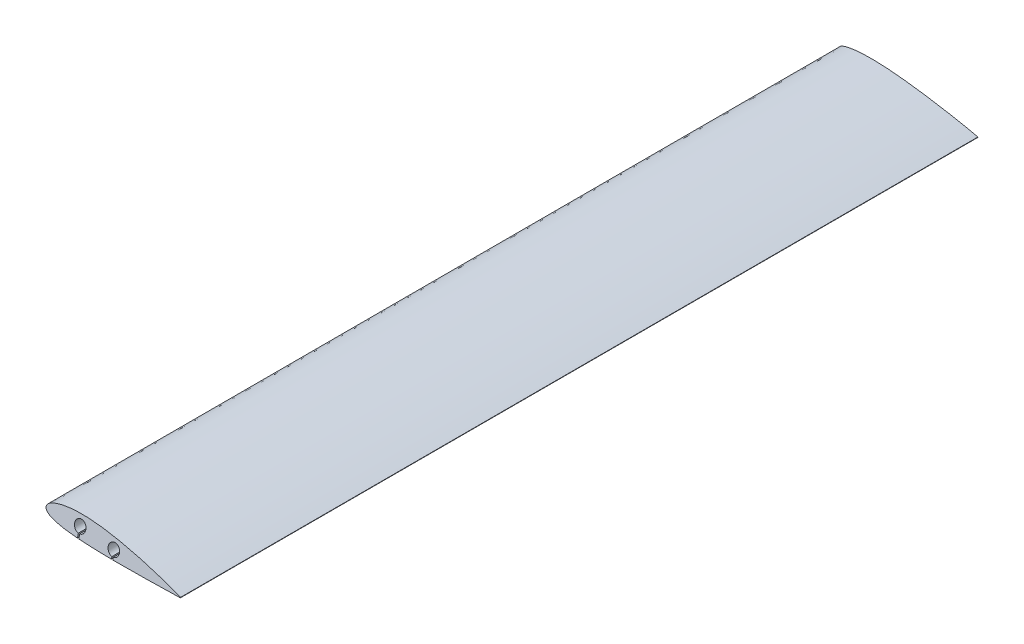
SolidWorks part; units mm, degrees
material "Custom Plastic"
ref_plane "Front Plane" through (0, 0, 0) normal (0, 0, 1) x (1, 0, 0)
ref_plane "Top Plane" through (0, 0, 0) normal (0, 1, 0) x (1, 0, 0)
ref_plane "Right Plane" through (0, 0, 0) normal (1, 0, 0) x (0, 0, -1)
curve "Curve1"
  spline degree 3 poles (119.72, -8.1948, 0) (119.6176, -8.1622, 0) (119.1985, -8.0289, 0) (118.2498, -7.745, 0) (116.6764, -7.2682, 0) (114.4937, -6.6229, 0) (111.726, -5.8198, 0) (108.3989, -4.8842, 0) (104.5474, -3.8358, 0) (100.2105, -2.7001, 0) (95.4335, -1.5003, 0) (90.2667, -0.2644, 0) (84.7642, 0.9828, 0) (78.9848, 2.2132, 0) (72.9906, 3.4008, 0) (66.8472, 4.5234, 0) (60.6201, 5.5483, 0) (54.3772, 6.4571, 0) (48.1692, 7.2302, 0) (42.0621, 7.8148, 0) (36.1259, 8.1773, 0) (30.4496, 8.3149, 0) (25.1001, 8.227, 0) (20.1405, 7.9255, 0) (15.6293, 7.4181, 0) (11.6181, 6.7322, 0) (8.1521, 5.8882, 0) (5.2655, 4.9177, 0) (2.98, 3.8441, 0) (1.3063, 2.6841, 0) (0.2335, 1.4154, 0) (-0.1257, -0.004, 0) (0.316, -1.3971, 0) (1.4469, -2.6023, 0) (3.1553, -3.6733, 0) (5.4426, -4.65, 0) (8.2964, -5.5286, 0) (11.6917, -6.304, 0) (15.5927, -6.9754, 0) (19.9599, -7.5398, 0) (24.7472, -8.002, 0) (29.9056, -8.3725, 0) (35.3823, -8.6597, 0) (41.1213, -8.8812, 0) (47.0817, -9.0555, 0) (53.2028, -9.1881, 0) (59.4204, -9.2536, 0) (65.6487, -9.2717, 0) (71.8184, -9.2592, 0) (77.8616, -9.2203, 0) (83.7119, -9.1645, 0) (89.3044, -9.1004, 0) (94.5769, -9.0293, 0) (99.4704, -8.9537, 0) (103.9296, -8.8805, 0) (107.904, -8.8075, 0) (111.3483, -8.7373, 0) (114.2228, -8.6769, 0) (116.4943, -8.6239, 0) (118.1358, -8.5859, 0) (119.1326, -8.5579, 0) (119.5801, -8.549, 0) (119.6954, -8.5467, 0) knots 0 0 0 0 0.001308 0.005358 0.012063 0.021337 0.033087 0.047171 0.063441 0.081714 0.101785 0.123442 0.146433 0.170517 0.195424 0.220875 0.246594 0.272302 0.297725 0.322799 0.347029 0.370162 0.391954 0.412188 0.43067 0.447231 0.461732 0.474085 0.484276 0.492392 0.498749 0.5041 0.509453 0.51579 0.523838 0.533885 0.546005 0.560171 0.576284 0.594211 0.613803 0.634869 0.65721 0.680611 0.704835 0.729853 0.755197 0.780583 0.805729 0.830359 0.854204 0.877002 0.898494 0.918443 0.936623 0.952826 0.966868 0.978592 0.987852 0.994547 0.998596 1 1 1 1
sketch "Sketch4" plane through (0, 0, 0) normal (0, 0, 1) x (1, 0, 0)
  line L0 (119.72, -8.1948) -> (119.6954, -8.5467)
  line L1 (0, 0) -> (162.2931, 0) construction
  spline S2 degree 3 poles (1370.0357, 3790.6471) (156.0859, -40.1115) (140.424, -14.3791) (118.2498, -7.745) (116.6764, -7.2682) (114.4937, -6.6229) (111.726, -5.8198) (108.3989, -4.8842) (104.5474, -3.8358) (100.2105, -2.7001) (95.4335, -1.5003) (90.2667, -0.2644) (84.7642, 0.9828) (78.9848, 2.2132) (72.9906, 3.4008) (66.8472, 4.5234) (60.6201, 5.5483) (54.3772, 6.4571) (48.1692, 7.2302) (42.0621, 7.8148) (36.1259, 8.1773) (30.4496, 8.3149) (25.1001, 8.227) (20.1405, 7.9255) (15.6293, 7.4181) (11.6181, 6.7322) (8.1521, 5.8882) (5.2655, 4.9177) (2.98, 3.8441) (1.3063, 2.6841) (0.2335, 1.4154) (-0.1257, -0.004) (0.316, -1.3971) (1.4469, -2.6023) (3.1553, -3.6733) (5.4426, -4.65) (8.2964, -5.5286) (11.6917, -6.304) (15.5927, -6.9754) (19.9599, -7.5398) (24.7472, -8.002) (29.9056, -8.3725) (35.3823, -8.6597) (41.1213, -8.8812) (47.0817, -9.0555) (53.2028, -9.1881) (59.4204, -9.2536) (65.6487, -9.2717) (71.8184, -9.2592) (77.8616, -9.2203) (83.7119, -9.1645) (89.3044, -9.1004) (94.5769, -9.0293) (99.4704, -8.9537) (103.9296, -8.8805) (107.904, -8.8075) (111.3483, -8.7373) (114.2228, -8.6769) (116.4943, -8.6239) (118.1358, -8.5859) (148.3455, -7.7372) (178.3806, -23.1567) (115.1651, 3990.3657) knots -0.26989 -0.26989 -0.26989 -0.26989 0.001308 0.005358 0.012063 0.021337 0.033087 0.047171 0.063441 0.081714 0.101785 0.123442 0.146433 0.170517 0.195424 0.220875 0.246594 0.272302 0.297725 0.322799 0.347029 0.370162 0.391954 0.412188 0.43067 0.447231 0.461732 0.474085 0.484276 0.492392 0.498749 0.5041 0.509453 0.51579 0.523838 0.533885 0.546005 0.560171 0.576284 0.594211 0.613803 0.634869 0.65721 0.680611 0.704835 0.729853 0.755197 0.780583 0.805729 0.830359 0.854204 0.877002 0.898494 0.918443 0.936623 0.952826 0.966868 0.978592 0.987852 0.994547 0.998596 1.35602 1.35602 1.35602 1.35602 only from (119.72, -8.1948) to (119.6954, -8.5467)
  spline S3 degree 3 poles (119.72, -8.1948) (119.6176, -8.1622) (119.1985, -8.0289) (118.2498, -7.745) (116.6764, -7.2682) (114.4937, -6.6229) (111.726, -5.8198) (108.3989, -4.8842) (104.5474, -3.8358) (100.2105, -2.7001) (95.4335, -1.5003) (90.2667, -0.2644) (84.7642, 0.9828) (78.9848, 2.2132) (72.9906, 3.4008) (66.8472, 4.5234) (60.6201, 5.5483) (54.3772, 6.4571) (48.1692, 7.2302) (42.0621, 7.8148) (36.1259, 8.1773) (30.4496, 8.3149) (25.1001, 8.227) (20.1405, 7.9255) (15.6293, 7.4181) (11.6181, 6.7322) (8.1521, 5.8882) (5.2655, 4.9177) (2.98, 3.8441) (1.3063, 2.6841) (0.2335, 1.4154) (-0.1257, -0.004) (0.316, -1.3971) (1.4469, -2.6023) (3.1553, -3.6733) (5.4426, -4.65) (8.2964, -5.5286) (11.6917, -6.304) (15.5927, -6.9754) (19.9599, -7.5398) (24.7472, -8.002) (29.9056, -8.3725) (35.3823, -8.6597) (41.1213, -8.8812) (47.0817, -9.0555) (53.2028, -9.1881) (59.4204, -9.2536) (65.6487, -9.2717) (71.8184, -9.2592) (77.8616, -9.2203) (83.7119, -9.1645) (89.3044, -9.1004) (94.5769, -9.0293) (99.4704, -8.9537) (103.9296, -8.8805) (107.904, -8.8075) (111.3483, -8.7373) (114.2228, -8.6769) (116.4943, -8.6239) (118.1358, -8.5859) (119.1326, -8.5579) (119.5801, -8.549) (119.6954, -8.5467) knots 0 0 0 0 0.001308 0.005358 0.012063 0.021337 0.033087 0.047171 0.063441 0.081714 0.101785 0.123442 0.146433 0.170517 0.195424 0.220875 0.246594 0.272302 0.297725 0.322799 0.347029 0.370162 0.391954 0.412188 0.43067 0.447231 0.461732 0.474085 0.484276 0.492392 0.498749 0.5041 0.509453 0.51579 0.523838 0.533885 0.546005 0.560171 0.576284 0.594211 0.613803 0.634869 0.65721 0.680611 0.704835 0.729853 0.755197 0.780583 0.805729 0.830359 0.854204 0.877002 0.898494 0.918443 0.936623 0.952826 0.966868 0.978592 0.987852 0.994547 0.998596 1 1 1 1
  dimension "D1" = 0
extrude "Boss-Extrude2" add sketch "Sketch4" along normal mid plane 700
sketch "Sketch5" plane through (0, 0, -350) normal (0, 0, -1) x (-1, 0, 0)
  line L1 (-30, 0) -> (-29.4, 0) construction
  line L2 (-29.4, 0) -> (-29.4, -8.3234)
  line L3 (-30, 0) -> (-30.6, 0) construction
  line L4 (-30.6, 0) -> (-30.6, -8.3975)
  line L5 (-60, -2.5) -> (-59.4, -2.5) construction
  line L6 (-119.72, -8.1948) -> (-119.6954, -8.5467)
  line L7 (-119.72, -8.1948) -> (-119.6954, -8.5467)
  line L8 (-59.4, -2.5) -> (-59.4, -9.2455)
  line L9 (-60, -2.5) -> (-60.6, -2.5) construction
  line L10 (-60.6, -2.5) -> (-60.6, -9.2528)
  circle A0 centre (-30, 0) radius 4.75 construction
  circle A1 centre (-60, -2.5) radius 4.95
  circle A2 centre (-30, 0) radius 4.95
  circle A4 centre (-60, -2.5) radius 4.75 construction
  spline S0 degree 3 poles (-119.72, -8.1948) (-119.6176, -8.1622) (-119.1985, -8.0289) (-118.2498, -7.745) (-116.6764, -7.2682) (-114.4937, -6.6229) (-111.726, -5.8198) (-108.3989, -4.8842) (-104.5474, -3.8358) (-100.2105, -2.7001) (-95.4335, -1.5003) (-90.2667, -0.2644) (-84.7642, 0.9828) (-78.9848, 2.2132) (-72.9906, 3.4008) (-66.8472, 4.5234) (-60.6201, 5.5483) (-54.3772, 6.4571) (-48.1692, 7.2302) (-42.0621, 7.8148) (-36.1259, 8.1773) (-30.4496, 8.3149) (-25.1001, 8.227) (-20.1405, 7.9255) (-15.6293, 7.4181) (-11.6181, 6.7322) (-8.1521, 5.8882) (-5.2655, 4.9177) (-2.98, 3.8441) (-1.3063, 2.6841) (-0.2335, 1.4154) (0.1257, -0.004) (-0.316, -1.3971) (-1.4469, -2.6023) (-3.1553, -3.6733) (-5.4426, -4.65) (-8.2964, -5.5286) (-11.6917, -6.304) (-15.5927, -6.9754) (-19.9599, -7.5398) (-24.7472, -8.002) (-29.9056, -8.3725) (-35.3823, -8.6597) (-41.1213, -8.8812) (-47.0817, -9.0555) (-53.2028, -9.1881) (-59.4204, -9.2536) (-65.6487, -9.2717) (-71.8184, -9.2592) (-77.8616, -9.2203) (-83.7119, -9.1645) (-89.3044, -9.1004) (-94.5769, -9.0293) (-99.4704, -8.9537) (-103.9296, -8.8805) (-107.904, -8.8075) (-111.3483, -8.7373) (-114.2228, -8.6769) (-116.4943, -8.6239) (-118.1358, -8.5859) (-119.1326, -8.5579) (-119.5801, -8.549) (-119.6954, -8.5467) knots 0 0 0 0 0.001308 0.005358 0.012063 0.021337 0.033087 0.047171 0.063441 0.081714 0.101785 0.123442 0.146433 0.170517 0.195424 0.220875 0.246594 0.272302 0.297725 0.322799 0.347029 0.370162 0.391954 0.412188 0.43067 0.447231 0.461732 0.474085 0.484276 0.492392 0.498749 0.5041 0.509453 0.51579 0.523838 0.533885 0.546005 0.560171 0.576284 0.594211 0.613803 0.634869 0.65721 0.680611 0.704835 0.729853 0.755197 0.780583 0.805729 0.830359 0.854204 0.877002 0.898494 0.918443 0.936623 0.952826 0.966868 0.978592 0.987852 0.994547 0.998596 1 1 1 1 construction
  spline S3 degree 3 poles (-115.1725, 3989.8946) (-178.3782, -23.1555) (-148.3443, -7.7372) (-118.1358, -8.5859) (-116.4943, -8.6239) (-114.2228, -8.6769) (-111.3483, -8.7373) (-107.904, -8.8075) (-103.9296, -8.8805) (-99.4704, -8.9537) (-94.5769, -9.0293) (-89.3044, -9.1004) (-83.7119, -9.1645) (-77.8616, -9.2203) (-71.8184, -9.2592) (-65.6487, -9.2717) (-59.4204, -9.2536) (-53.2028, -9.1881) (-47.0817, -9.0555) (-41.1213, -8.8812) (-35.3823, -8.6597) (-29.9056, -8.3725) (-24.7472, -8.002) (-19.9599, -7.5398) (-15.5927, -6.9754) (-11.6917, -6.304) (-8.2964, -5.5286) (-5.4426, -4.65) (-3.1553, -3.6733) (-1.4469, -2.6023) (-0.316, -1.3971) (0.1257, -0.004) (-0.2335, 1.4154) (-1.3063, 2.6841) (-2.98, 3.8441) (-5.2655, 4.9177) (-8.1521, 5.8882) (-11.6181, 6.7322) (-15.6293, 7.4181) (-20.1405, 7.9255) (-25.1001, 8.227) (-30.4496, 8.3149) (-36.1259, 8.1773) (-42.0621, 7.8148) (-48.1692, 7.2302) (-54.3772, 6.4571) (-60.6201, 5.5483) (-66.8472, 4.5234) (-72.9906, 3.4008) (-78.9848, 2.2132) (-84.7642, 0.9828) (-90.2667, -0.2644) (-95.4335, -1.5003) (-100.2105, -2.7001) (-104.5474, -3.8358) (-108.3989, -4.8842) (-111.726, -5.8198) (-114.4937, -6.6229) (-116.6764, -7.2682) (-118.2498, -7.745) (-140.4231, -14.3788) (-156.0845, -40.1093) (-1369.8814, 3790.1602) knots -0.356006 -0.356006 -0.356006 -0.356006 0.001404 0.005453 0.012148 0.021408 0.033132 0.047174 0.063377 0.081557 0.101506 0.122998 0.145796 0.169641 0.194271 0.219417 0.244803 0.270147 0.295165 0.319389 0.34279 0.365131 0.386197 0.405789 0.423716 0.439829 0.453995 0.466115 0.476162 0.48421 0.490547 0.4959 0.501251 0.507608 0.515724 0.525915 0.538268 0.552769 0.56933 0.587812 0.608046 0.629838 0.652971 0.677201 0.702275 0.727698 0.753406 0.779125 0.804576 0.829483 0.853567 0.876558 0.898215 0.918286 0.936559 0.952829 0.966913 0.978663 0.987937 0.994642 0.998692 1.269879 1.269879 1.269879 1.269879 only from (-119.6954, -8.5467) to (-119.72, -8.1948)
  spline S4 degree 3 poles (-119.6954, -8.5467) (-119.5801, -8.549) (-119.1326, -8.5579) (-118.1358, -8.5859) (-116.4943, -8.6239) (-114.2228, -8.6769) (-111.3483, -8.7373) (-107.904, -8.8075) (-103.9296, -8.8805) (-99.4704, -8.9537) (-94.5769, -9.0293) (-89.3044, -9.1004) (-83.7119, -9.1645) (-77.8616, -9.2203) (-71.8184, -9.2592) (-65.6487, -9.2717) (-59.4204, -9.2536) (-53.2028, -9.1881) (-47.0817, -9.0555) (-41.1213, -8.8812) (-35.3823, -8.6597) (-29.9056, -8.3725) (-24.7472, -8.002) (-19.9599, -7.5398) (-15.5927, -6.9754) (-11.6917, -6.304) (-8.2964, -5.5286) (-5.4426, -4.65) (-3.1553, -3.6733) (-1.4469, -2.6023) (-0.316, -1.3971) (0.1257, -0.004) (-0.2335, 1.4154) (-1.3063, 2.6841) (-2.98, 3.8441) (-5.2655, 4.9177) (-8.1521, 5.8882) (-11.6181, 6.7322) (-15.6293, 7.4181) (-20.1405, 7.9255) (-25.1001, 8.227) (-30.4496, 8.3149) (-36.1259, 8.1773) (-42.0621, 7.8148) (-48.1692, 7.2302) (-54.3772, 6.4571) (-60.6201, 5.5483) (-66.8472, 4.5234) (-72.9906, 3.4008) (-78.9848, 2.2132) (-84.7642, 0.9828) (-90.2667, -0.2644) (-95.4335, -1.5003) (-100.2105, -2.7001) (-104.5474, -3.8358) (-108.3989, -4.8842) (-111.726, -5.8198) (-114.4937, -6.6229) (-116.6764, -7.2682) (-118.2498, -7.745) (-119.1985, -8.0289) (-119.6176, -8.1622) (-119.72, -8.1948) knots 0 0 0 0 0.001404 0.005453 0.012148 0.021408 0.033132 0.047174 0.063377 0.081557 0.101506 0.122998 0.145796 0.169641 0.194271 0.219417 0.244803 0.270147 0.295165 0.319389 0.34279 0.365131 0.386197 0.405789 0.423716 0.439829 0.453995 0.466115 0.476162 0.48421 0.490547 0.4959 0.501251 0.507608 0.515724 0.525915 0.538268 0.552769 0.56933 0.587812 0.608046 0.629838 0.652971 0.677201 0.702275 0.727698 0.753406 0.779125 0.804576 0.829483 0.853567 0.876558 0.898215 0.918286 0.936559 0.952829 0.966913 0.978663 0.987937 0.994642 0.998692 1 1 1 1
  dimension "D1" = 9.5
  dimension "D6" = 0.2
  dimension "D12" = 9.5
  dimension "D2" = 0.6
  dimension "D3" = 0.6
  dimension "D4" = 30
  dimension "D8" = 30
  dimension "D9" = 2.5
  dimension "D10" = 0.6
  dimension "D11" = 0.6
  dimension "D5" = 0
  dimension "D7" = 0.2
extrude "Cut-Extrude1" cut sketch "Sketch5" against normal through all
sketch "Sketch6" plane through (0, 0, 0) normal (1, 0, 0) x (0, 0, -1)
  line L0 (350, -9.5) -> (345.1227, 12.5)
  line L1 (345.1227, 12.5) -> (350, 12.5)
  line L2 (350, 12.5) -> (350, -9.5)
  line L3 (350, 0) -> (352.9573, 0) construction
  dimension "D1" = 12.5
  dimension "D2" = 22
  dimension "D3" = 9.5
extrude "Cut-Extrude2" cut sketch "Sketch6" along normal through all both and the other way through all
mirror "Mirror1" about plane through (0, 0, 0) normal (0, 0, 1) of "Cut-Extrude2"
sketch "Sketch7" plane through (0, 0, 0) normal (0, 0, 1) x (1, 0, 0)
  line L0 (0, 0) -> (119.7077, -8.3708)
  line L1 (119.72, -8.1948) -> (119.6954, -8.5467) construction
sketch "Sketch1" plane through (0, 0, 0) normal (0, 0, 1) x (1, 0, 0)
  line L0 (0, 0) -> (-120, 0)
  spline S0 degree 3 poles (-120, 0) (-86.4181, 33.0029) (-44.1117, 7.7348) (0, 0) knots 0 0 0 0 1 1 1 1
  dimension "D1" = 120
sketch "Sketch10" plane through (0, 73.5132, -331.5964) normal (0, 0.2164, -0.9763) x (-1, 0, 0)
  line L10 (-29.4, -80.3308) -> (-29.4, -83.8235)
  line L11 (-119.72, -83.6918) -> (-119.6954, -84.0523)
  line L12 (-60.6, -84.7754) -> (-60.6, -82.8915)
  line L13 (-59.4, -82.8915) -> (-59.4, -84.768)
  line L14 (-30.6, -83.8994) -> (-30.6, -80.3308)
  line L15 (-29.4, -80.3308) -> (-29.4, -83.8235)
  line L16 (-119.72, -83.6918) -> (-119.6954, -84.0523)
  line L17 (-60.6, -84.7754) -> (-60.6, -82.8915)
  line L18 (-59.4, -82.8915) -> (-59.4, -84.768)
  line L19 (-30.6, -83.8994) -> (-30.6, -80.3308)
  ellipse E4 centre (-30, -75.298) end of major axis (-30, -80.3682) minor radius 4.95 (-29.4, -80.3308) -> (-30.6, -80.3308) ccw
  ellipse E5 centre (-60, -77.8587) end of major axis (-60, -82.9289) minor radius 4.95 (-59.4, -82.8915) -> (-60.6, -82.8915) ccw
  ellipse E6 centre (-30, -75.298) end of major axis (-30, -80.3682) minor radius 4.95 (-29.4, -80.3308) -> (-30.6, -80.3308) ccw
  ellipse E7 centre (-60, -77.8587) end of major axis (-60, -82.9289) minor radius 4.95 (-59.4, -82.8915) -> (-60.6, -82.8915) ccw
  spline S6 degree 3 poles (-129.0038, -3067.1467) (-294.6774, 64.5062) (-148.6922, -98.237) (-17.9123, -82.7534) (-16.2774, -82.5299) (-13.0267, -81.9958) (-11.4096, -81.6863) (-9.0051, -81.1129) (-8.2061, -80.9027) (-6.6242, -80.4309) (-5.8432, -80.169) (-4.6937, -79.7184) (-4.3144, -79.5582) (-3.5663, -79.2103) (-3.1961, -79.0219) (-2.4776, -78.6127) (-2.13, -78.3914) (-1.6362, -78.0203) (-1.4761, -77.8901) (-1.1671, -77.6141) (-1.0176, -77.4673) (-0.7415, -77.1576) (-0.6143, -76.9942) (-0.3882, -76.6449) (-0.2903, -76.4593) (-0.1348, -76.0775) (-0.0757, -75.8799) (-0.0026, -75.4686) (0.009, -75.2604) (-0.0187, -74.85) (-0.0572, -74.6439) (-0.1751, -74.2444) (-0.2536, -74.0525) (-0.4465, -73.6832) (-0.5601, -73.5076) (-0.8084, -73.1781) (-0.9439, -73.0226) (-1.2314, -72.7252) (-1.3839, -72.5827) (-1.6973, -72.3124) (-1.8588, -72.1844) (-2.355, -71.8179) (-2.7013, -71.5968) (-3.413, -71.1833) (-3.7803, -70.9912) (-4.5232, -70.6346) (-4.8987, -70.47) (-6.0342, -70.005) (-6.803, -69.7345) (-8.3571, -69.2478) (-9.9271, -68.8138) (-11.5221, -68.463) (-13.1272, -68.1454) (-13.9353, -68.0034) (-17.9689, -67.3685) (-21.1974, -67.085) (-27.6561, -66.7928) (-30.8863, -66.7855) (-37.3484, -66.9826) (-40.5801, -67.1867) (-45.4286, -67.6248) (-47.046, -67.7927) (-50.2759, -68.1647) (-51.887, -68.3684) (-56.7111, -69.0208) (-59.9156, -69.5084) (-66.3051, -70.5725) (-69.4897, -71.1507) (-75.8419, -72.3842) (-79.0098, -73.0386) (-88.4895, -75.1104) (-94.778, -76.6335) (-104.1669, -79.1183) (-107.289, -79.9805) (-111.9602, -81.3289) (-113.5149, -81.7888) (-115.8444, -82.4906) (-116.6204, -82.7271) (-117.7833, -83.0861) (-118.1709, -83.2061) (-156.859, -95.1146) (-191.3126, -124.403) (407.6713, -3035.1854) knots -2.402462 -2.402462 -2.402462 -2.402462 0.0625 0.0625 0.09375 0.09375 0.125 0.125 0.140625 0.140625 0.15625 0.15625 0.164063 0.164063 0.171875 0.171875 0.179688 0.179688 0.183594 0.183594 0.1875 0.1875 0.191406 0.191406 0.195313 0.195313 0.199219 0.199219 0.203125 0.203125 0.207031 0.207031 0.210938 0.210938 0.214844 0.214844 0.21875 0.21875 0.222656 0.222656 0.226563 0.226563 0.234375 0.234375 0.242188 0.242188 0.25 0.25 0.265625 0.265625 0.28125 0.296875 0.296875 0.3125 0.3125 0.375 0.375 0.4375 0.4375 0.5 0.5 0.53125 0.53125 0.5625 0.5625 0.625 0.625 0.6875 0.6875 0.75 0.75 0.875 0.875 0.9375 0.9375 0.96875 0.96875 0.984375 0.984375 0.992188 0.992188 1.763921 1.763921 1.763921 1.763921 only from (-29.4, -83.8235) to (-119.72, -83.6918)
  spline S7 degree 3 poles (-285.2311, -3077.69) (-204.8189, -68.0593) (-161.4186, -82.9984) (-117.2335, -84.1142) (-116.618, -84.1285) (-114.7715, -84.1723) (-113.5405, -84.2002) (-109.8475, -84.2794) (-107.3854, -84.3298) (-99.999, -84.4648) (-95.0746, -84.5421) (-85.2255, -84.671) (-80.3008, -84.7244) (190.96, -86.5516) (458.0708, -25.0124) (758.3092, 2743.6823) knots -2.180934 -2.180934 -2.180934 -2.180934 0.03125 0.03125 0.0625 0.0625 0.125 0.125 0.25 0.25 0.5 0.5 0.75 0.75 14.269732 14.269732 14.269732 14.269732 only from (-119.6954, -84.0523) to (-60.6, -84.7754)
  spline S8 degree 3 poles (-580.6833, -3000.2145) (-466.5066, 26.805) (-257.5568, -88.4357) (-49.7952, -84.636) (-47.3948, -84.5775) (-42.5946, -84.4391) (-40.1949, -84.3584) (107.3754, -78.3122) (250.5806, -7.1829) (308.8579, 2879.7851) knots -21.134089 -21.134089 -21.134089 -21.134089 0.25 0.25 0.5 0.5 0.75 0.75 15.876916 15.876916 15.876916 15.876916 only from (-59.4, -84.768) to (-30.6, -83.8994)
  spline S9 degree 3 poles (-29.4, -83.8235) (-26.1092, -83.6082) (-22.8239, -83.335) (-17.9123, -82.7534) (-16.2774, -82.5299) (-13.0267, -81.9958) (-11.4096, -81.6863) (-9.0051, -81.1129) (-8.2061, -80.9027) (-6.6242, -80.4309) (-5.8432, -80.169) (-4.6937, -79.7184) (-4.3144, -79.5582) (-3.5663, -79.2103) (-3.1961, -79.0219) (-2.4776, -78.6127) (-2.13, -78.3914) (-1.6362, -78.0203) (-1.4761, -77.8901) (-1.1671, -77.6141) (-1.0176, -77.4673) (-0.7415, -77.1576) (-0.6143, -76.9942) (-0.3882, -76.6449) (-0.2903, -76.4593) (-0.1348, -76.0775) (-0.0757, -75.8799) (-0.0026, -75.4686) (0.009, -75.2604) (-0.0187, -74.85) (-0.0572, -74.6439) (-0.1751, -74.2444) (-0.2536, -74.0525) (-0.4465, -73.6832) (-0.5601, -73.5076) (-0.8084, -73.1781) (-0.9439, -73.0226) (-1.2314, -72.7252) (-1.3839, -72.5827) (-1.6973, -72.3124) (-1.8588, -72.1844) (-2.355, -71.8179) (-2.7013, -71.5968) (-3.413, -71.1833) (-3.7803, -70.9912) (-4.5232, -70.6346) (-4.8987, -70.47) (-6.0342, -70.005) (-6.803, -69.7345) (-8.3571, -69.2478) (-9.9271, -68.8138) (-11.5221, -68.463) (-13.1272, -68.1454) (-13.9353, -68.0034) (-17.9689, -67.3685) (-21.1974, -67.085) (-27.6561, -66.7928) (-30.8863, -66.7855) (-37.3484, -66.9826) (-40.5801, -67.1867) (-45.4286, -67.6248) (-47.046, -67.7927) (-50.2759, -68.1647) (-51.887, -68.3684) (-56.7111, -69.0208) (-59.9156, -69.5084) (-66.3051, -70.5725) (-69.4897, -71.1507) (-75.8419, -72.3842) (-79.0098, -73.0386) (-88.4895, -75.1104) (-94.778, -76.6335) (-104.1669, -79.1183) (-107.289, -79.9805) (-111.9602, -81.3289) (-113.5149, -81.7888) (-115.8444, -82.4906) (-116.6204, -82.7271) (-117.7833, -83.0861) (-118.1709, -83.2061) (-118.9464, -83.4448) (-119.3337, -83.5659) (-119.72, -83.6918) knots 0 0 0 0 0.0625 0.0625 0.09375 0.09375 0.125 0.125 0.140625 0.140625 0.15625 0.15625 0.164063 0.164063 0.171875 0.171875 0.179688 0.179688 0.183594 0.183594 0.1875 0.1875 0.191406 0.191406 0.195313 0.195313 0.199219 0.199219 0.203125 0.203125 0.207031 0.207031 0.210938 0.210938 0.214844 0.214844 0.21875 0.21875 0.222656 0.222656 0.226563 0.226563 0.234375 0.234375 0.242188 0.242188 0.25 0.25 0.265625 0.265625 0.28125 0.296875 0.296875 0.3125 0.3125 0.375 0.375 0.4375 0.4375 0.5 0.5 0.53125 0.53125 0.5625 0.5625 0.625 0.625 0.6875 0.6875 0.75 0.75 0.875 0.875 0.9375 0.9375 0.96875 0.96875 0.984375 0.984375 0.992188 0.992188 1 1 1 1
  spline S10 degree 3 poles (-119.6954, -84.0523) (-119.0799, -84.0648) (-118.4644, -84.0831) (-117.2335, -84.1142) (-116.618, -84.1285) (-114.7715, -84.1723) (-113.5405, -84.2002) (-109.8475, -84.2794) (-107.3854, -84.3298) (-99.999, -84.4648) (-95.0746, -84.5421) (-85.2255, -84.671) (-80.3008, -84.7244) (-70.4509, -84.7908) (-65.5257, -84.8023) (-60.6, -84.7754) knots 0 0 0 0 0.03125 0.03125 0.0625 0.0625 0.125 0.125 0.25 0.25 0.5 0.5 0.75 0.75 1 1 1 1
  spline S11 degree 3 poles (-59.4, -84.768) (-56.9983, -84.7514) (-54.597, -84.7238) (-49.7952, -84.636) (-47.3948, -84.5775) (-42.5946, -84.4391) (-40.1949, -84.3584) (-35.3965, -84.1618) (-32.9978, -84.0457) (-30.6, -83.8994) knots 0 0 0 0 0.25 0.25 0.5 0.5 0.75 0.75 1 1 1 1
  dimension "D1" = 0
